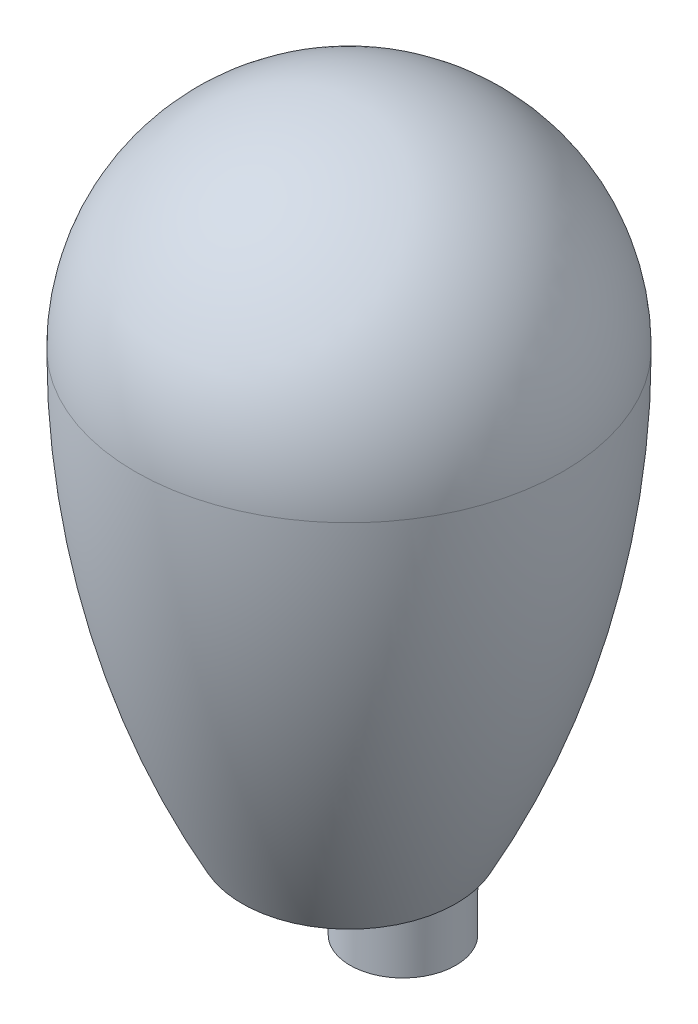
SolidWorks part; units mm, degrees
ref_plane "Front Plane" through (0, 0, 0) normal (0, 0, 1) x (1, 0, 0)
ref_plane "Top Plane" through (0, 0, 0) normal (0, 1, 0) x (1, 0, 0)
ref_plane "Right Plane" through (0, 0, 0) normal (1, 0, 0) x (0, 0, -1)
sketch "Sketch1" plane through (0, 0, 0) normal (0, 0, 1) x (1, 0, 0)
  line L0 (0, 0) -> (0, 3)
  line L1 (0, 0) -> (0.5, 0)
  arc A0 (-1, 2) -> (1, 2) centre (0, 2) cw construction
  arc A1 (1, 2) -> (0.5, 0) centre (-3.25, 2) cw
  arc A2 (0, 3) -> (1, 2) centre (0, 2) cw
  dimension "D1" = 2
  dimension "D2" = 1
  dimension "D3" = 0.5
  dimension "D4" = 2
revolve "Revolve2" add sketch "Sketch1" angle 360 about L0
sketch "Sketch2" plane through (0, 0, 0) normal (0, -1, 0) x (1, 0, 0)
  circle A0 centre (0.2525, 0) radius 0.2475
  circle A1 centre (-0.2525, 0) radius 0.2475
  circle A2 centre (0, 0) radius 0.5 construction
  dimension "D1" = 0.495
extrude "Boss-Extrude1" add sketch "Sketch2" along normal blind 0.25
other "CPoint1" parameters "Diameter"=1, "StubLength"=0
ref_axis "Axis1" through (0.2525, -10.25, 0) along (0, 1, 0)
other "CPoint2" parameters "Diameter"=1, "StubLength"=0
ref_axis "Axis2" through (-0.2525, -10.25, 0) along (0, 1, 0)
